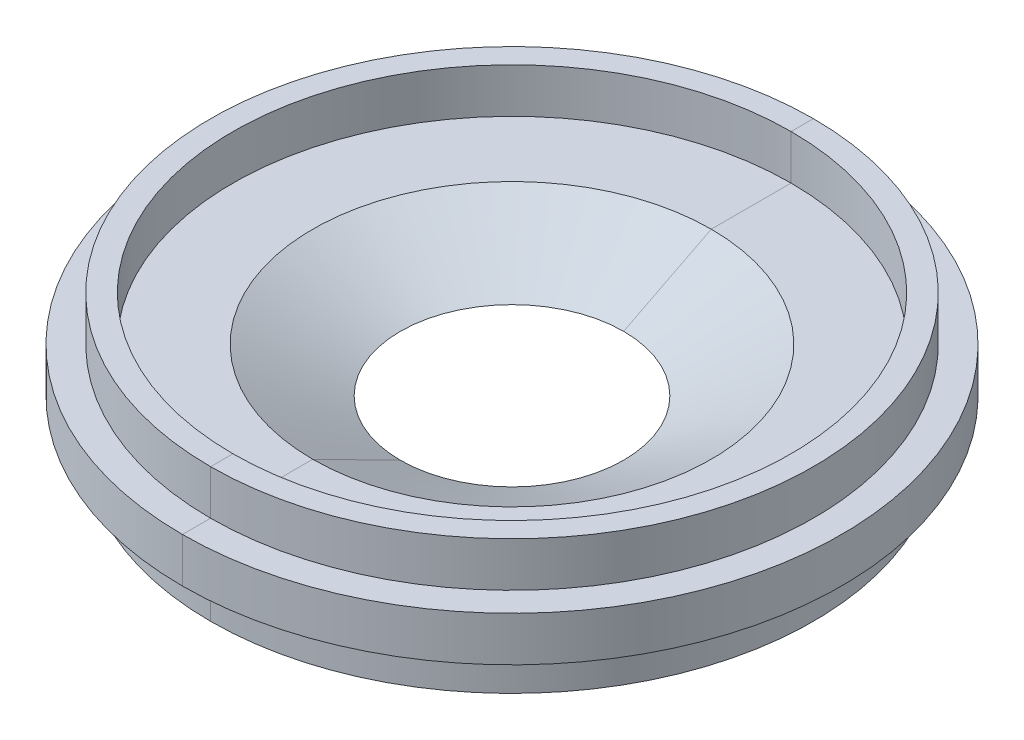
SolidWorks part; units mm, degrees
ref_plane "Front Plane" through (0, 0, 0) normal (0, 0, 1) x (1, 0, 0)
ref_plane "Top Plane" through (0, 0, 0) normal (0, 1, 0) x (1, 0, 0)
ref_plane "Right Plane" through (0, 0, 0) normal (1, 0, 0) x (0, 0, -1)
sketch "Sketch1" plane through (0, 0, 0) normal (0, 1, 0) x (1, 0, 0)
  circle A0 centre (0, 0) radius 93.726
  circle A1 centre (0, 0) radius 31.75
  dimension "D1" = 187.452
  dimension "D2" = 63.5
extrude "Boss-Extrude1" add sketch "Sketch1" along normal mid plane 12.7
sketch "Sketch5" plane through (0, 6.35, 0) normal (0, 1, 0) x (1, 0, 0)
  circle A0 centre (0, 0) radius 85.725
  circle A1 centre (0, 0) radius 79.375
  dimension "D1" = 171.45
  dimension "D2" = 158.75
extrude "Boss-Extrude2" add sketch "Sketch5" along normal blind 12.7
ref_plane "Plane1" through (0, 0, -85.725) normal (0, 0, -1) x (-1, 0, 0)
sketch "Sketch6" plane through (0, 0, -85.725) normal (0, 0, -1) x (-1, 0, 0)
  line L0 (0, 13.97) -> (0, -13.97) construction
  line L1 (93.726, 6.35) -> (-93.726, 6.35) construction
  circle A0 centre (0, 12.7) radius 1.4351
  dimension "D1" = 2.8702
  dimension "D2" = 6.35
extrude "Cut-Extrude1" [suppressed] cut sketch "Sketch6" against normal blind 12.7
pattern_circular "CirPattern1" [suppressed] count 12 over 360 reverse direction yes of bodies 107
mirror "Mirror1" about plane through (0, 0, 0) normal (0, 1, 0) of "CirPattern1", "Cut-Extrude1", "Boss-Extrude2"
sketch "Sketch7" plane through (0, 19.05, 0) normal (0, 1, 0) x (1, 0, 0)
  line L0 (-25.7878, 75.0692) -> (-28.1663, 80.9657)
  line L1 (28.1663, 80.9657) -> (25.7878, 75.0692)
  arc A0 (28.1663, 80.9657) -> (-28.1663, 80.9657) centre (0, 0) ccw
  circle A1 centre (0, 0) radius 85.725 construction
  arc A2 (25.7878, 75.0692) -> (-25.7878, 75.0692) centre (0, 0) ccw
  circle A3 centre (0, 0) radius 79.375 construction
extrude "Boss-Extrude3" add sketch "Sketch7" against normal up to surface (12.7 mm away) up to face at (0, 6.35, 85.725)
mirror "Mirror3" about plane through (0, 0, 0) normal (0, 1, 0) of "Boss-Extrude3"
mirror "Mirror4" about plane through (0, 0, 0) normal (0, 0, 1) of "Boss-Extrude3"
mirror "Mirror5" about plane through (0, 0, 0) normal (0, 1, 0) of "Mirror4"
sketch "Sketch4" plane through (0, 0, 0) normal (0, 0, 1) x (1, 0, 0)
  line L0 (0, 23.2786) -> (0, -14.9525) construction
sketch "Sketch3" plane through (0, 0, 0) normal (0, 0, 1) x (1, 0, 0)
  line L0 (-31.75, -6.35) -> (-56.6752, 6.35)
  line L1 (93.726, 6.35) -> (-93.726, 6.35) construction
  line L2 (-56.6752, 6.35) -> (-31.75, 6.35)
  line L3 (-31.75, 6.35) -> (-31.75, -6.35)
  line L4 (-31.75, -6.35) -> (31.75, -6.35) construction
  line L5 (31.75, 6.35) -> (-31.75, 6.35) construction
  dimension "D1" = 27
revolve "Cut-Revolve1" cut sketch "Sketch3" angle 360 about L0
split "Split1" trim tools "Right Plane" bodies to split 103 resulting bodies 104 105
